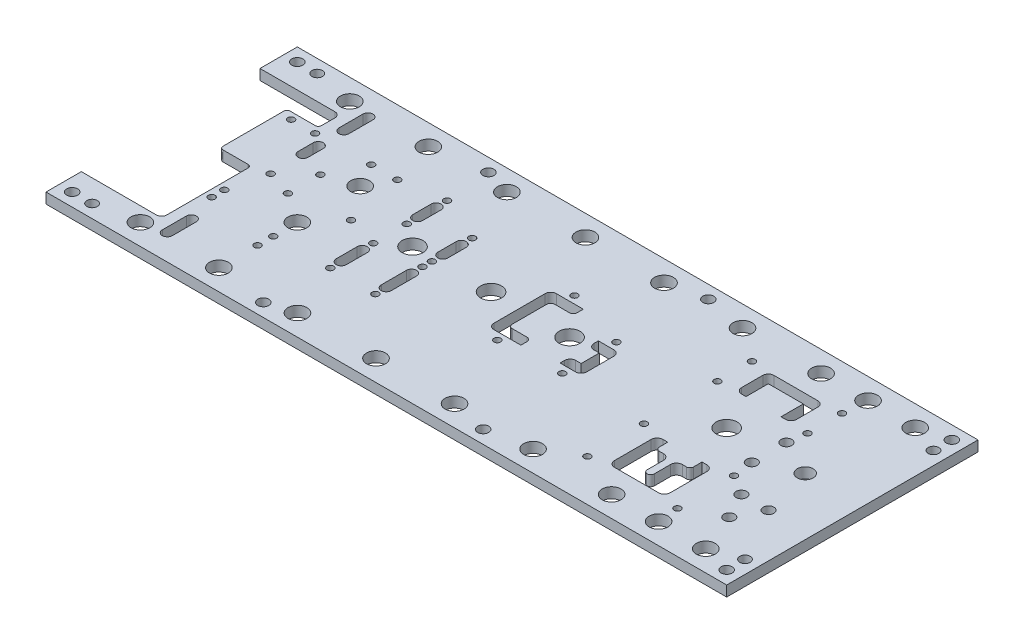
SolidWorks part; units mm, degrees
material "K110"
ref_plane "Front Plane" through (0, 0, 0) normal (0, 0, 1) x (1, 0, 0)
ref_plane "Top Plane" through (0, 0, 0) normal (0, 1, 0) x (1, 0, 0)
ref_plane "Right Plane" through (0, 0, 0) normal (1, 0, 0) x (0, 0, -1)
sketch "Sketch1" plane through (0, 0, 0) normal (0, 1, 0) x (1, 0, 0)
  line L1 (-325, -120) -> (325, -120)
  line L2 (-325, -120) -> (-325, 120)
  line L3 (-325, 120) -> (325, 120)
  line L4 (325, -120) -> (325, 120)
  line L5 (-325, -120) -> (325, 120) construction
  line L6 (-325, 120) -> (325, -120) construction
  point P0 (0, 0)
  dimension "D1" = 650
  dimension "D2" = 240
extrude "Boss-Extrude1" add sketch "Sketch1" against normal blind 10
sketch "Sketch2" plane through (0, -10, 0) normal (0, -1, 0) x (1, 0, 0)
  circle A0 centre (-254.87, 100) radius 9 construction
  circle A1 centre (-254.87, -100) radius 9
  circle A2 centre (-254.87, -100) radius 9
  circle A3 centre (285, -100) radius 9
  circle A4 centre (285, -100) radius 9
  circle A5 centre (120.13, 100) radius 9
  circle A6 centre (120.13, 100) radius 9
  circle A7 centre (120.13, -100) radius 9
  circle A8 centre (120.13, -100) radius 9
  circle A9 centre (45.13, 100) radius 9
  circle A10 centre (45.13, 100) radius 9
  circle A11 centre (240, 100) radius 9
  circle A12 centre (240, 100) radius 9
  circle A13 centre (240, -100) radius 9
  circle A14 centre (240, -100) radius 9
  circle A15 centre (195.13, -100) radius 9
  circle A16 centre (195.13, -100) radius 9
  circle A17 centre (285, 100) radius 9
  circle A18 centre (285, 100) radius 9
  circle A19 centre (-104.87, -100) radius 9
  circle A20 centre (-104.87, -100) radius 9
  circle A21 centre (-179.87, 100) radius 9
  circle A22 centre (-179.87, 100) radius 9
  circle A23 centre (-179.87, -100) radius 9
  circle A24 centre (-179.87, -100) radius 9
  circle A25 centre (45.13, -100) radius 9
  circle A26 centre (45.13, -100) radius 9
  circle A27 centre (-29.87, 100) radius 9
  circle A28 centre (-29.87, 100) radius 9
  circle A29 centre (-29.87, -100) radius 9
  circle A30 centre (-29.87, -100) radius 9
  circle A31 centre (-104.87, 100) radius 9
  circle A32 centre (-104.87, 100) radius 9
  circle A33 centre (195.13, 100) radius 9
  circle A34 centre (195.13, 100) radius 9
  circle A35 centre (-254.87, 100) radius 9
  circle A36 centre (195.13, -9.86) radius 10 construction
  circle A37 centre (45.13, -9.86) radius 10 construction
  circle A38 centre (-29.87, -9.86) radius 10 construction
  circle A39 centre (-104.87, -9.86) radius 10 construction
  circle A40 centre (-179.87, 25.14) radius 9 construction
  circle A41 centre (-179.87, -34.86) radius 9 construction
  circle A42 centre (195.13, -9.86) radius 10
  circle A43 centre (45.13, -9.86) radius 10
  circle A44 centre (-29.87, -9.86) radius 10
  circle A45 centre (-104.87, -9.86) radius 10
  circle A46 centre (-179.87, 25.14) radius 9
  circle A47 centre (-179.87, -34.86) radius 9
  dimension "D1" = 0
  dimension "D2" = 0
  dimension "D3" = 0
  dimension "D4" = 0
  dimension "D5" = 0
  dimension "D6" = 0
  dimension "D7" = 0
  dimension "D8" = 0
  dimension "D9" = 0
  dimension "D10" = 0
  dimension "D11" = 0
  dimension "D12" = 0
  dimension "D13" = 0
  dimension "D14" = 0
  dimension "D15" = 0
  dimension "D16" = 0
  dimension "D17" = 0
extrude "Cut-Extrude1" cut sketch "Sketch2" against normal up to next
hole_wizard "M6 Clearance Hole1" positions "Sketch7" profile "Sketch6" hole size "M6" standard "ISO" end condition through all
sketch "Sketch7" plane through (0, -10, 0) normal (0, -1, 0) x (-1, 0, 0)
  line L0 (232.87, -8.64) -> (232.87, 13.36) construction
  point P0 (-238.13, -26.14)
  point P3 (-152.13, -26.14)
  point P6 (-152.13, -80.14)
  point P9 (-238.13, -80.14)
  point P12 (-238.13, 77)
  point P15 (-152.13, 77)
  point P18 (-152.13, 44)
  point P21 (-238.13, 44)
  point P24 (-71.5, -23.4862)
  point P27 (-71.5, 28.2062)
  point P30 (-12.94, -26.9862)
  point P33 (-12.94, 46.7062)
  point P36 (83.37, 45.36)
  point P39 (83.37, 6.86)
  point P42 (126.37, 25.86)
  point P45 (126.37, 64.36)
  point P48 (83.37, -2.14)
  point P51 (126.37, -6.14)
  point P54 (126.37, -47.14)
  point P57 (83.37, -47.14)
  point P60 (156.12, 2.36)
  point P63 (208.37, -5.64)
  point P66 (208.37, 25.36)
  point P69 (192.37, 57.86)
  point P72 (167.37, 57.86)
  point P75 (179.87, -48.14)
  point P78 (179.87, -63.14)
  point P81 (241.62, -33.14)
  point P84 (241.62, -45.14)
  point P87 (232.87, 2.36)
  point P91 (267.87, 56.92)
  point P94 (245.0007, 56.92)
sketch "Sketch6" plane through (238.13, -10, 26.14) normal (1, 0, 0) x (0, 0, -1)
  line L0 (0, 0) -> (0, 10)
  line L1 (0, 10) -> (3.2, 10)
  line L2 (3.2, 10) -> (3.2, 0.025)
  line L3 (3.2, 0.025) -> (3.225, 0)
  line L5 (3.225, 0) -> (0, 0)
  line L6 (-3.2, 0.025) -> (-3.225, 0) construction
  line L11 (0, -6.35) -> (0, 107.95) construction
  dimension "Thru Hole Dia." = 6.4
  dimension "Thru Hole Depth" = 10
  dimension "Near C'Sink Dia." = 6.45
  dimension "Near C'Sink Angle" = 90
sketch "Sketch8" plane through (0, 0, 0) normal (0, 1, 0) x (1, 0, 0)
  line L0 (-325, -86.2624) -> (-253.37, -86.2624) construction
  line L2 (-248.37, -52.14) -> (-248.37, -14.64) construction
  line L3 (-278.37, 33.36) -> (-278.37, -0.64) construction
  line L4 (-248.37, 63.475) -> (-248.37, 79.36) construction
  line L5 (-253.37, 84.36) -> (-325, 84.36) construction
  line L6 (-325, -86.2624) -> (-253.37, -86.2624)
  line L8 (-248.37, -81.2624) -> (-248.37, -3.64)
  line L9 (-278.37, 63.48) -> (-278.37, -0.64)
  line L10 (-248.37, 63.48) -> (-248.37, 79.36)
  line L11 (-253.37, 84.36) -> (-325, 84.36)
  line L12 (-273.87, 63.48) -> (-237.87, 63.48) construction
  line L13 (-278.37, 63.48) -> (-248.37, 63.48)
  line L14 (-325, 84.36) -> (-325, -86.2624)
  line L15 (-251.37, -0.64) -> (-270.37, -0.64) construction
  line L16 (-251.37, -0.64) -> (-278.37, -0.64)
  arc A0 (-253.37, -86.2624) -> (-248.37, -81.2624) centre (-253.37, -81.2624) ccw construction
  arc A1 (-248.37, 79.36) -> (-253.37, 84.36) centre (-253.37, 79.36) ccw construction
  arc A2 (-253.37, -86.2624) -> (-248.37, -81.2624) centre (-253.37, -81.2624) ccw
  arc A3 (-248.37, 79.36) -> (-253.37, 84.36) centre (-253.37, 79.36) ccw
  arc A4 (-248.37, -3.64) -> (-251.37, -0.64) centre (-251.37, -3.64) ccw construction
  arc A5 (-248.37, -3.64) -> (-251.37, -0.64) centre (-251.37, -3.64) ccw
extrude "Cut-Extrude2" cut sketch "Sketch8" against normal up to next
fillet "Fillet1" radius 3 3 edges at (-248.37, -5, -63.48) (-278.37, -5, -63.48) (-278.37, -5, 0.64)
sketch "Sketch12" plane through (0, -10, 0) normal (0, -1, 0) x (1, 0, 0)
  line L18 (211.8377, -45.0677) -> (211.8377, -66.3477)
  line L19 (178.4223, -66.3477) -> (178.4223, -45.0677)
  line L20 (211.8377, -66.3477) -> (178.4223, -66.3477)
  line L21 (216.13, -45.0677) -> (211.8377, -45.0677)
  line L22 (221.4223, -70.64) -> (221.4223, -50.36)
  line L23 (195.13, -75.9323) -> (216.13, -75.9323)
  line L24 (174.13, -75.9323) -> (195.13, -75.9323)
  line L25 (178.4223, -45.0677) -> (174.13, -45.0677)
  line L26 (168.8377, -50.36) -> (168.8377, -70.64)
  line L27 (211.8377, -45.0677) -> (211.8377, -66.3477)
  line L28 (178.4223, -66.3477) -> (178.4223, -45.0677)
  line L29 (211.8377, -66.3477) -> (178.4223, -66.3477)
  line L30 (216.13, -45.0677) -> (211.8377, -45.0677)
  line L31 (221.4223, -70.64) -> (221.4223, -50.36)
  line L32 (195.13, -75.9323) -> (216.13, -75.9323)
  line L33 (174.13, -75.9323) -> (195.13, -75.9323)
  line L34 (178.4223, -45.0677) -> (174.13, -45.0677)
  line L35 (168.8377, -50.36) -> (168.8377, -70.64)
  line L51 (211.5164, 30.0264) -> (216.13, 30.0264)
  line L52 (221.7436, 35.64) -> (221.7436, 53.14)
  line L53 (221.7436, 53.14) -> (221.7436, 70.64)
  line L54 (216.13, 76.2536) -> (174.13, 76.2536)
  line L55 (168.5164, 70.64) -> (168.5164, 35.64)
  line L56 (174.13, 30.0264) -> (178.7436, 30.0264)
  line L57 (211.5164, 38.14) -> (211.5164, 30.0264)
  line L58 (204.13, 41.5264) -> (208.13, 41.5264)
  line L59 (198.5164, 62.64) -> (198.5164, 47.14)
  line L60 (191.7436, 47.14) -> (191.7436, 62.64)
  line L61 (182.13, 41.5264) -> (186.13, 41.5264)
  line L62 (178.7436, 30.0264) -> (178.7436, 38.14)
  line L63 (211.5164, 30.0264) -> (216.13, 30.0264)
  line L64 (221.7436, 35.64) -> (221.7436, 53.14)
  line L65 (221.7436, 53.14) -> (221.7436, 70.64)
  line L66 (216.13, 76.2536) -> (174.13, 76.2536)
  line L67 (168.5164, 70.64) -> (168.5164, 35.64)
  line L68 (174.13, 30.0264) -> (178.7436, 30.0264)
  line L69 (211.5164, 38.14) -> (211.5164, 30.0264)
  line L70 (204.13, 41.5264) -> (208.13, 41.5264)
  line L71 (198.5164, 62.64) -> (198.5164, 47.14)
  line L72 (191.7436, 47.14) -> (191.7436, 62.64)
  line L73 (182.13, 41.5264) -> (186.13, 41.5264)
  line L74 (178.7436, 30.0264) -> (178.7436, 38.14)
  arc A8 (221.4223, -50.36) -> (216.13, -45.0677) centre (216.13, -50.36) ccw
  arc A9 (216.13, -75.9323) -> (221.4223, -70.64) centre (216.13, -70.64) ccw
  arc A10 (174.13, -45.0677) -> (168.8377, -50.36) centre (174.13, -50.36) ccw
  arc A11 (168.8377, -70.64) -> (174.13, -75.9323) centre (174.13, -70.64) ccw
  arc A12 (221.4223, -50.36) -> (216.13, -45.0677) centre (216.13, -50.36) ccw
  arc A13 (216.13, -75.9323) -> (221.4223, -70.64) centre (216.13, -70.64) ccw
  arc A14 (174.13, -45.0677) -> (168.8377, -50.36) centre (174.13, -50.36) ccw
  arc A15 (168.8377, -70.64) -> (174.13, -75.9323) centre (174.13, -70.64) ccw
  arc A30 (216.13, 30.0264) -> (221.7436, 35.64) centre (216.13, 35.64) ccw
  arc A31 (221.7436, 70.64) -> (216.13, 76.2536) centre (216.13, 70.64) ccw
  arc A32 (174.13, 76.2536) -> (168.5164, 70.64) centre (174.13, 70.64) ccw
  arc A33 (168.5164, 35.64) -> (174.13, 30.0264) centre (174.13, 35.64) ccw
  arc A34 (211.5164, 38.14) -> (208.13, 41.5264) centre (208.13, 38.14) ccw
  arc A35 (198.5164, 47.14) -> (204.13, 41.5264) centre (204.13, 47.14) ccw
  arc A36 (198.5164, 62.64) -> (191.7436, 62.64) centre (195.13, 62.64) ccw
  arc A37 (186.13, 41.5264) -> (191.7436, 47.14) centre (186.13, 47.14) ccw
  arc A38 (182.13, 41.5264) -> (178.7436, 38.14) centre (182.13, 38.14) ccw
  arc A39 (216.13, 30.0264) -> (221.7436, 35.64) centre (216.13, 35.64) ccw
  arc A40 (221.7436, 70.64) -> (216.13, 76.2536) centre (216.13, 70.64) ccw
  arc A41 (174.13, 76.2536) -> (168.5164, 70.64) centre (174.13, 70.64) ccw
  arc A42 (168.5164, 35.64) -> (174.13, 30.0264) centre (174.13, 35.64) ccw
  arc A43 (211.5164, 38.14) -> (208.13, 41.5264) centre (208.13, 38.14) ccw
  arc A44 (198.5164, 47.14) -> (204.13, 41.5264) centre (204.13, 47.14) ccw
  arc A45 (198.5164, 62.64) -> (191.7436, 62.64) centre (195.13, 62.64) ccw
  arc A46 (186.13, 41.5264) -> (191.7436, 47.14) centre (186.13, 47.14) ccw
  arc A47 (182.13, 41.5264) -> (178.7436, 38.14) centre (182.13, 38.14) ccw
  circle A1945 centre (270.13, 62.64) radius 5.1136
  circle A1946 centre (270.13, 62.64) radius 5.1136
  circle A1948 centre (283.13, 38.14) radius 5.1136
  circle A1949 centre (283.13, 38.14) radius 5.1136
  circle A1951 centre (257.13, 38.14) radius 5.1136
  circle A1952 centre (257.13, 38.14) radius 5.1136
  circle A1954 centre (270.13, -9.86) radius 7.6136
  circle A1955 centre (270.13, -9.86) radius 7.6136
  circle A1957 centre (235.63, -26.36) radius 5.1136
  circle A1958 centre (235.63, -26.36) radius 5.1136
  circle A1960 centre (235.63, 6.64) radius 5.1136
  circle A1961 centre (235.63, 6.64) radius 5.1136
  dimension "D1" = 1.6
  dimension "D2" = 1.6
  dimension "D3" = 1.6
  dimension "D4" = 1.6
  dimension "D5" = 1.6
  dimension "D6" = 1.6
  dimension "D7" = 1.6
  dimension "D8" = 1.6
extrude "Cut-Extrude3" cut sketch "Sketch12" against normal up to next
sketch "Sketch13" plane through (0, -10, 0) normal (0, -1, 0) x (1, 0, 0)
  line L72 (61.8377, 15.9323) -> (61.8377, 11.64)
  line L73 (67.13, 6.3477) -> (72.3377, 6.3477)
  line L74 (72.3377, 6.3477) -> (72.3377, -11.0677)
  line L75 (72.3377, -11.0677) -> (67.13, -11.0677)
  line L76 (61.8377, -16.36) -> (61.8377, -20.6523)
  line L77 (76.63, 15.9323) -> (61.8377, 15.9323)
  line L78 (81.9223, -2.36) -> (81.9223, 10.64)
  line L79 (81.9223, -15.36) -> (81.9223, -2.36)
  line L80 (61.8377, -20.6523) -> (76.63, -20.6523)
  line L81 (61.8377, 15.9323) -> (61.8377, 11.64)
  line L82 (67.13, 6.3477) -> (72.3377, 6.3477)
  line L83 (72.3377, 6.3477) -> (72.3377, -11.0677)
  line L84 (72.3377, -11.0677) -> (67.13, -11.0677)
  line L85 (61.8377, -16.36) -> (61.8377, -20.6523)
  line L86 (76.63, 15.9323) -> (61.8377, 15.9323)
  line L87 (81.9223, -2.36) -> (81.9223, 10.64)
  line L88 (81.9223, -15.36) -> (81.9223, -2.36)
  line L89 (61.8377, -20.6523) -> (76.63, -20.6523)
  line L99 (2.63, -39.6523) -> (28.4223, -39.6523)
  line L100 (-2.6623, -13.23) -> (-2.6623, -34.36)
  line L101 (-2.6623, 14.64) -> (-2.6623, -13.23)
  line L102 (28.4223, 19.9323) -> (2.63, 19.9323)
  line L103 (28.4223, 14.14) -> (28.4223, 19.9323)
  line L104 (28.4223, -39.6523) -> (28.4223, -33.86)
  line L105 (24.63, -30.0677) -> (10.63, -30.0677)
  line L106 (6.9223, -26.36) -> (6.9223, 6.64)
  line L107 (10.63, 10.3477) -> (24.63, 10.3477)
  line L108 (2.63, -39.6523) -> (28.4223, -39.6523)
  line L109 (-2.6623, -13.23) -> (-2.6623, -34.36)
  line L110 (-2.6623, 14.64) -> (-2.6623, -13.23)
  line L111 (28.4223, 19.9323) -> (2.63, 19.9323)
  line L112 (28.4223, 14.14) -> (28.4223, 19.9323)
  line L113 (28.4223, -39.6523) -> (28.4223, -33.86)
  line L114 (24.63, -30.0677) -> (10.63, -30.0677)
  line L115 (6.9223, -26.36) -> (6.9223, 6.64)
  line L116 (10.63, 10.3477) -> (24.63, 10.3477)
  arc A48 (61.8377, 11.64) -> (67.13, 6.3477) centre (67.13, 11.64) ccw
  arc A49 (67.13, -11.0677) -> (61.8377, -16.36) centre (67.13, -16.36) ccw
  arc A50 (81.9223, 10.64) -> (76.63, 15.9323) centre (76.63, 10.64) ccw
  arc A51 (76.63, -20.6523) -> (81.9223, -15.36) centre (76.63, -15.36) ccw
  arc A52 (61.8377, 11.64) -> (67.13, 6.3477) centre (67.13, 11.64) ccw
  arc A53 (67.13, -11.0677) -> (61.8377, -16.36) centre (67.13, -16.36) ccw
  arc A54 (81.9223, 10.64) -> (76.63, 15.9323) centre (76.63, 10.64) ccw
  arc A55 (76.63, -20.6523) -> (81.9223, -15.36) centre (76.63, -15.36) ccw
  arc A62 (-2.6623, -34.36) -> (2.63, -39.6523) centre (2.63, -34.36) ccw
  arc A63 (2.63, 19.9323) -> (-2.6623, 14.64) centre (2.63, 14.64) ccw
  arc A64 (28.4223, -33.86) -> (24.63, -30.0677) centre (24.63, -33.86) ccw
  arc A65 (6.9223, -26.36) -> (10.63, -30.0677) centre (10.63, -26.36) ccw
  arc A66 (10.63, 10.3477) -> (6.9223, 6.64) centre (10.63, 6.64) ccw
  arc A67 (24.63, 10.3477) -> (28.4223, 14.14) centre (24.63, 14.14) ccw
  arc A68 (-2.6623, -34.36) -> (2.63, -39.6523) centre (2.63, -34.36) ccw
  arc A69 (2.63, 19.9323) -> (-2.6623, 14.64) centre (2.63, 14.64) ccw
  arc A70 (28.4223, -33.86) -> (24.63, -30.0677) centre (24.63, -33.86) ccw
  arc A71 (6.9223, -26.36) -> (10.63, -30.0677) centre (10.63, -26.36) ccw
  arc A72 (10.63, 10.3477) -> (6.9223, 6.64) centre (10.63, 6.64) ccw
  arc A73 (24.63, 10.3477) -> (28.4223, 14.14) centre (24.63, 14.14) ccw
  dimension "D1" = 1.6
  dimension "D2" = 1.6
extrude "Cut-Extrude4" cut sketch "Sketch13" against normal up to next
sketch "Sketch14" plane through (0, -10, 0) normal (0, -1, 0) x (1, 0, 0)
  line L8 (-88.1623, -17.31) -> (-88.1623, -34.91)
  line L9 (-78.5777, -26.11) -> (-78.5777, -17.31)
  line L10 (-78.5777, -34.91) -> (-78.5777, -26.11)
  line L11 (-88.1623, -17.31) -> (-88.1623, -34.91)
  line L12 (-78.5777, -26.11) -> (-78.5777, -17.31)
  line L13 (-78.5777, -34.91) -> (-78.5777, -26.11)
  line L17 (-78.5777, 12.59) -> (-78.5777, 24.64)
  line L18 (-88.1623, 36.69) -> (-88.1623, 12.59)
  line L19 (-78.5777, 24.64) -> (-78.5777, 36.69)
  line L20 (-78.5777, 12.59) -> (-78.5777, 24.64)
  line L21 (-88.1623, 36.69) -> (-88.1623, 12.59)
  line L22 (-78.5777, 24.64) -> (-78.5777, 36.69)
  line L26 (-131.2322, 36.69) -> (-131.2322, 16.59)
  line L27 (-121.5078, 26.64) -> (-121.5078, 36.69)
  line L28 (-121.5078, 16.59) -> (-121.5078, 26.64)
  line L29 (-131.2322, 36.69) -> (-131.2322, 16.59)
  line L30 (-121.5078, 26.64) -> (-121.5078, 36.69)
  line L31 (-121.5078, 16.59) -> (-121.5078, 26.64)
  line L35 (-131.1623, -36.31) -> (-131.1623, -53.91)
  line L36 (-121.5777, -45.11) -> (-121.5777, -36.31)
  line L37 (-121.5777, -53.91) -> (-121.5777, -45.11)
  line L38 (-131.1623, -36.31) -> (-131.1623, -53.91)
  line L39 (-121.5777, -45.11) -> (-121.5777, -36.31)
  line L40 (-121.5777, -53.91) -> (-121.5777, -45.11)
  arc A6 (-88.1623, -34.91) -> (-78.5777, -34.91) centre (-83.37, -34.91) ccw
  arc A7 (-78.5777, -17.31) -> (-88.1623, -17.31) centre (-83.37, -17.31) ccw
  arc A8 (-88.1623, -34.91) -> (-78.5777, -34.91) centre (-83.37, -34.91) ccw
  arc A9 (-78.5777, -17.31) -> (-88.1623, -17.31) centre (-83.37, -17.31) ccw
  arc A12 (-88.1623, 12.59) -> (-78.5777, 12.59) centre (-83.37, 12.59) ccw
  arc A13 (-78.5777, 36.69) -> (-88.1623, 36.69) centre (-83.37, 36.69) ccw
  arc A14 (-88.1623, 12.59) -> (-78.5777, 12.59) centre (-83.37, 12.59) ccw
  arc A15 (-78.5777, 36.69) -> (-88.1623, 36.69) centre (-83.37, 36.69) ccw
  arc A18 (-131.2322, 16.59) -> (-121.5078, 16.59) centre (-126.37, 16.59) ccw
  arc A19 (-121.5078, 36.69) -> (-131.2322, 36.69) centre (-126.37, 36.69) ccw
  arc A20 (-131.2322, 16.59) -> (-121.5078, 16.59) centre (-126.37, 16.59) ccw
  arc A21 (-121.5078, 36.69) -> (-131.2322, 36.69) centre (-126.37, 36.69) ccw
  arc A24 (-131.1623, -53.91) -> (-121.5777, -53.91) centre (-126.37, -53.91) ccw
  arc A25 (-121.5777, -36.31) -> (-131.1623, -36.31) centre (-126.37, -36.31) ccw
  arc A26 (-131.1623, -53.91) -> (-121.5777, -53.91) centre (-126.37, -53.91) ccw
  arc A27 (-121.5777, -36.31) -> (-131.1623, -36.31) centre (-126.37, -36.31) ccw
  dimension "D1" = 1.6
  dimension "D2" = 1.6
  dimension "D3" = 1.6
  dimension "D4" = 1.6
extrude "Cut-Extrude5" cut sketch "Sketch14" against normal up to next
sketch "Sketch15" plane through (0, -10, 0) normal (0, -1, 0) x (1, 0, 0)
  line L6 (-228.5777, -95.77) -> (-228.5777, -84.32)
  line L7 (-228.5777, -84.32) -> (-228.5777, -72.87)
  line L8 (-238.1623, -72.87) -> (-238.1623, -95.77)
  line L9 (-228.5777, -95.77) -> (-228.5777, -84.32)
  line L10 (-228.5777, -84.32) -> (-228.5777, -72.87)
  line L11 (-238.1623, -72.87) -> (-238.1623, -95.77)
  line L15 (-238.1623, -33.86) -> (-238.1623, -48.36)
  line L16 (-228.5777, -41.11) -> (-228.5777, -33.86)
  line L17 (-228.5777, -48.36) -> (-228.5777, -41.11)
  line L18 (-238.1623, -33.86) -> (-238.1623, -48.36)
  line L19 (-228.5777, -41.11) -> (-228.5777, -33.86)
  line L20 (-228.5777, -48.36) -> (-228.5777, -41.11)
  line L24 (-238.1623, 95.77) -> (-238.1623, 72.87)
  line L25 (-228.5777, 84.32) -> (-228.5777, 95.77)
  line L26 (-228.5777, 72.87) -> (-228.5777, 84.32)
  line L27 (-238.1623, 95.77) -> (-238.1623, 72.87)
  line L28 (-228.5777, 84.32) -> (-228.5777, 95.77)
  line L29 (-228.5777, 72.87) -> (-228.5777, 84.32)
  arc A4 (-228.5777, -72.87) -> (-238.1623, -72.87) centre (-233.37, -72.87) ccw
  arc A5 (-238.1623, -95.77) -> (-228.5777, -95.77) centre (-233.37, -95.77) ccw
  arc A6 (-228.5777, -72.87) -> (-238.1623, -72.87) centre (-233.37, -72.87) ccw
  arc A7 (-238.1623, -95.77) -> (-228.5777, -95.77) centre (-233.37, -95.77) ccw
  arc A10 (-228.5777, -33.86) -> (-238.1623, -33.86) centre (-233.37, -33.86) ccw
  arc A11 (-238.1623, -48.36) -> (-228.5777, -48.36) centre (-233.37, -48.36) ccw
  arc A12 (-228.5777, -33.86) -> (-238.1623, -33.86) centre (-233.37, -33.86) ccw
  arc A13 (-238.1623, -48.36) -> (-228.5777, -48.36) centre (-233.37, -48.36) ccw
  arc A16 (-228.5777, 95.77) -> (-238.1623, 95.77) centre (-233.37, 95.77) ccw
  arc A17 (-238.1623, 72.87) -> (-228.5777, 72.87) centre (-233.37, 72.87) ccw
  arc A18 (-228.5777, 95.77) -> (-238.1623, 95.77) centre (-233.37, 95.77) ccw
  arc A19 (-238.1623, 72.87) -> (-228.5777, 72.87) centre (-233.37, 72.87) ccw
  dimension "D1" = 1.6
  dimension "D2" = 1.6
  dimension "D3" = 1.6
extrude "Cut-Extrude6" cut sketch "Sketch15" against normal up to next
hole_wizard "M10 Clearance Hole1" positions "Sketch28" profile "Sketch17" hole size "M10" standard "ISO" end condition through all
sketch "Sketch28" plane through (0, -10, 0) normal (0, -1, 0) x (-1, 0, 0)
  point P52 (-312.5, 107.5)
  point P55 (-312.5, -107.5)
  point P58 (-80, 107.5)
  point P61 (130, 107.5)
  point P64 (312.5, 107.5)
  point P67 (312.5, -107.5)
  point P70 (130, -107.5)
  point P73 (-80, -107.5)
sketch "Sketch17" plane through (312.5, -10, -107.5) normal (1, 0, 0) x (0, 0, -1)
  line L0 (0, 0) -> (0, 10)
  line L1 (0, 10) -> (5.25, 10)
  line L2 (5.25, 10) -> (5.25, 0)
  line L5 (5.25, 0) -> (0, 0)
  line L11 (0, -6.35) -> (0, 107.95) construction
  dimension "Thru Hole Dia." = 10.5
  dimension "Thru Hole Depth" = 10
hole_wizard "Ø10.0mm Dowel Hole1" positions "Sketch23" profile "Sketch21" hole size "Ø10.0" standard "ISO" end condition through all
sketch "Sketch23" plane through (0, -10, 0) normal (0, -1, 0) x (-1, 0, 0)
  point P0 (-312.5, 90)
  point P3 (-312.5, -90)
  point P6 (293.5, -107.5)
  point P9 (293.5, 107.5)
sketch "Sketch21" plane through (312.5, -10, -90) normal (1, 0, 0) x (0, 0, -1)
  line L0 (0, 0) -> (0, 10)
  line L1 (0, 10) -> (5, 10)
  line L2 (5, 10) -> (5, 0)
  line L5 (5, 0) -> (0, 0)
  line L11 (0, -6.35) -> (0, 107.95) construction
  dimension "Thru Hole Dia." = 10
  dimension "Thru Hole Depth" = 10
